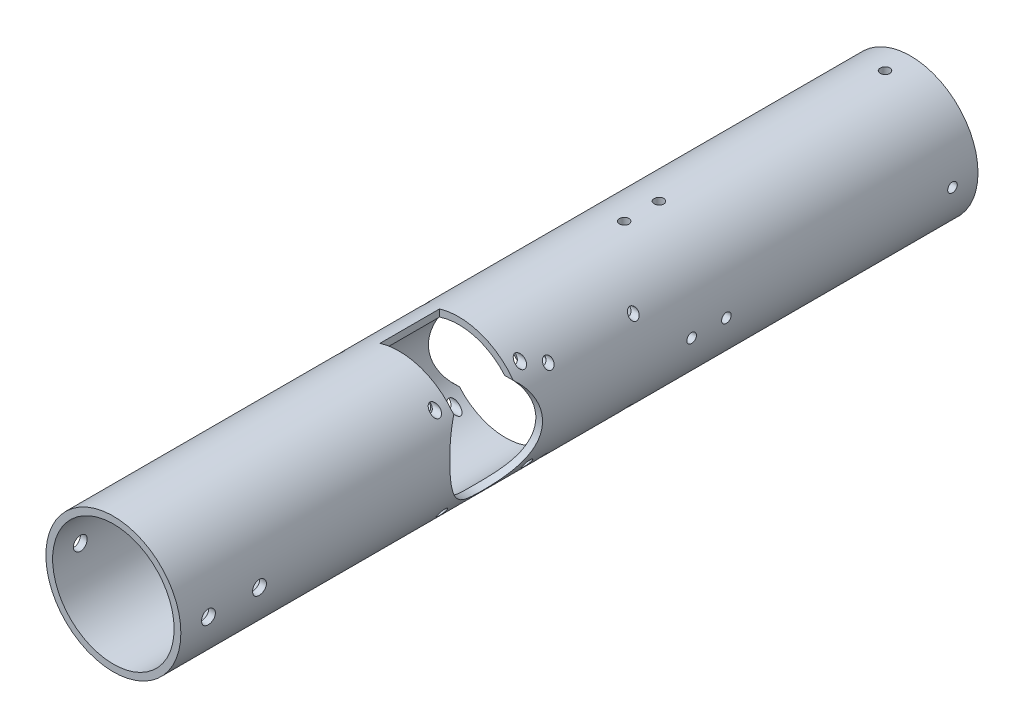
SolidWorks part; units mm, degrees
material "6061 Alloy"
ref_plane "Front Plane" through (0, 0, 0) normal (0, 0, 1) x (1, 0, 0)
ref_plane "Top Plane" through (0, 0, 0) normal (0, 1, 0) x (1, 0, 0)
ref_plane "Right Plane" through (0, 0, 0) normal (1, 0, 0) x (0, 0, -1)
sketch "Sketch1" plane through (0, 0, 0) normal (0, 0, 1) x (1, 0, 0)
  circle A0 centre (0, 0) radius 31.75
  circle A1 centre (0, 0) radius 28.575
  dimension "D1" = 63.5
  dimension "D2" = 57.15
extrude "Boss-Extrude1" add sketch "Sketch1" along normal blind 125 and the other way blind 250 contours A1 | A0 region at (0, 0, 0)
sketch "Sketch2" plane through (0, 0, 0) normal (1, 0, 0) x (0, 0, -1)
  circle A2 centre (73.488, -2) radius 21.75
  dimension "D1" = 43.5
  dimension "D2" = 73.488
  dimension "D3" = 2
extrude "Cut-Extrude1" cut sketch "Sketch2" against normal through all
sketch "Sketch3" plane through (0, 0, 0) normal (1, 0, 0) x (0, 0, -1)
  circle A1 centre (23.45, 2) radius 21.75
  dimension "D1" = 23.45
  dimension "D2" = 43.5
  dimension "D3" = 2
extrude "Cut-Extrude2" cut sketch "Sketch3" along normal through all
sketch "Sketch5" plane through (0, 0, 0) normal (1, 0, 0) x (0, 0, -1)
  line L1 (87.488, -12.75) -> (59.488, -12.75)
  line L2 (87.488, -12.75) -> (87.488, -34.75)
  line L3 (87.488, -34.75) -> (59.488, -34.75)
  line L4 (59.488, -12.75) -> (59.488, -34.75)
  line L5 (87.488, -12.75) -> (59.488, -34.75) construction
  line L6 (87.488, -34.75) -> (59.488, -12.75) construction
  circle A0 centre (73.488, -2) radius 21.75 construction
  circle A1 centre (73.488, -2) radius 21.75 construction
  circle A2 centre (73.488, -2) radius 21.75 construction
  point P0 (73.488, -23.75)
  dimension "D1" = 28
  dimension "D2" = 22
extrude "Cut-Extrude4" cut sketch "Sketch5" against normal through all from offset 9
sketch "Sketch6" plane through (0, 0, 0) normal (1, 0, 0) x (0, 0, -1)
  line L1 (9.45, 34.75) -> (37.45, 34.75)
  line L2 (9.45, 34.75) -> (9.45, 12.75)
  line L3 (9.45, 12.75) -> (37.45, 12.75)
  line L4 (37.45, 34.75) -> (37.45, 12.75)
  line L5 (9.45, 34.75) -> (37.45, 12.75) construction
  line L6 (9.45, 12.75) -> (37.45, 34.75) construction
  circle A0 centre (23.45, 2) radius 21.75 construction
  circle A1 centre (23.45, 2) radius 21.75 construction
  circle A2 centre (23.45, 2) radius 21.75 construction
  point P0 (23.45, 23.75)
  dimension "D1" = 28
  dimension "D2" = 22
extrude "Cut-Extrude5" cut sketch "Sketch6" along normal through all from offset 9 offset against normal yes
sketch "Sketch10" plane through (0, 0, 0) normal (1, 0, 0) x (0, 0, -1)
  line L1 (113.488, 38) -> (33.488, 38)
  line L2 (113.488, 38) -> (113.488, -42)
  line L3 (113.488, -42) -> (33.488, -42)
  line L4 (33.488, 38) -> (33.488, -42)
  line L5 (113.488, 38) -> (33.488, -42) construction
  line L6 (113.488, -42) -> (33.488, 38) construction
  point P0 (73.488, -2)
  dimension "D1" = 80
  dimension "D2" = 80
sketch "Sketch11" plane through (0, 0, 0) normal (1, 0, 0) x (0, 0, -1)
  line L0 (113.488, 38) -> (33.488, -42) construction
  line L1 (113.488, -42) -> (33.488, 38) construction
  line L2 (51.738, -2) -> (95.238, -2) construction
  line L3 (53.488, 18) -> (53.488, -22) construction
  circle A0 centre (93.488, 18) radius 2
  circle A1 centre (53.488, 18) radius 2
  circle A2 centre (53.488, -22) radius 2
  circle A3 centre (93.488, -22) radius 2
  arc A4 (87.488, -18.6452) -> (59.488, -18.6452) centre (73.488, -2) ccw construction
  arc A5 (87.488, -18.6452) -> (59.488, -18.6452) centre (73.488, -2) ccw construction
  point P18 (53.488, -2)
  dimension "D5" = 4
  dimension "D1" = 40
extrude "Cut-Extrude8" cut sketch "Sketch11" against normal through all both and the other way through all
sketch "Sketch12" plane through (0, 0, 0) normal (1, 0, 0) x (0, 0, -1)
  line L0 (-125, 31.75) -> (-125, -31.75) construction
  circle A0 centre (-112, 0) radius 3.25
  circle A1 centre (-88, 0) radius 3.25
  dimension "D2" = 6.5
  dimension "D3" = 24
  dimension "D4" = 13
extrude "Cut-Extrude10" cut sketch "Sketch12" against normal through all both and the other way through all
sketch "Sketch13" plane through (0, 0, 0) normal (0, 1, 0) x (1, 0, 0)
  line L0 (0, -34.925) -> (0, 34.925) construction
  line L1 (28.575, 250) -> (-28.575, 250) construction
  line L2 (0, 250) -> (0, -125) construction
  circle A0 centre (0, 238) radius 2.25
  circle A1 centre (0, 205.9) radius 2.25 construction
  dimension "D2" = 4.5
  dimension "D3" = 32.1
  dimension "D1" = 12
extrude "Cut-Extrude11" cut sketch "Sketch13" against normal through all both and the other way through all
sketch "Sketch14" plane through (0, 0, 0) normal (1, 0, 0) x (0, 0, -1)
  line L0 (3.45, -18) -> (3.45, 22) construction
  line L1 (-1.55, 27) -> (48.45, 27) construction
  line L2 (-1.55, 27) -> (-1.55, -23) construction
  line L3 (-1.55, -23) -> (48.45, -23) construction
  line L4 (48.45, 27) -> (48.45, -23) construction
  line L5 (-1.55, 27) -> (48.45, -23) construction
  line L6 (-1.55, -23) -> (48.45, 27) construction
  circle A0 centre (3.45, 22) radius 2
  circle A1 centre (43.45, 22) radius 2
  circle A2 centre (43.45, -18) radius 2
  circle A3 centre (3.45, -18) radius 2
  point P0 (23.45, 2)
  point P14 (3.45, 2)
  dimension "D5" = 4
  dimension "D1" = 40
  dimension "D2" = 50
sketch "Sketch15" plane through (0, 0, 0) normal (1, 0, 0) x (0, 0, -1)
  circle A0 centre (3.45, 22) radius 2
  circle A1 centre (43.45, 22) radius 2
  circle A2 centre (43.45, -18) radius 2
  circle A3 centre (3.45, -18) radius 2
  dimension "D1" = 4
extrude "Cut-Extrude12" cut sketch "Sketch15" against normal through all and the other way through all
hole_wizard "M4 Clearance Hole1" positions "Sketch18" profile "Sketch19" hole size "M4" standard "ANSI Metric" end condition through all
sketch "Sketch18" plane through (0, 0, 0) normal (1, 0, 0) x (0, 0, -1)
  circle A0 centre (3.45, 22) radius 2 construction
  circle A1 centre (43.45, 22) radius 2 construction
  circle A2 centre (3.45, -18) radius 2 construction
  circle A3 centre (43.45, -18) radius 2 construction
  point P0 (3.45, 22)
  point P2 (43.45, 22)
  point P4 (3.45, -18)
  point P6 (43.45, -18)
  point P20 (93.488, 18)
  point P23 (53.488, 18)
  point P26 (93.488, -22)
  point P29 (53.488, -22)
sketch "Sketch19" plane through (0, 22, -3.45) normal (0, 1, 0) x (0, 0, 1)
  line L0 (0, 0) -> (0, 31.75)
  line L1 (0, 31.75) -> (2.25, 31.75)
  line L2 (2.25, 31.75) -> (2.25, 0)
  line L5 (2.25, 0) -> (0, 0)
  line L11 (0, -6.35) -> (0, 107.95) construction
  dimension "Thru Hole Dia." = 4.5
  dimension "Thru Hole Depth" = 31.75
mirror "Mirror1" about plane through (0, 0, 0) normal (1, 0, 0) of "M4 Clearance Hole1"
sketch "Sketch21" plane through (0, 0, -250) normal (0, 0, -1) x (-1, 0, 0)
  circle A0 centre (0, 0) radius 30
  dimension "D1" = 60
extrude "Cut-Extrude14" cut sketch "Sketch21" against normal blind 7
pattern_circular "CirPattern1" count 2 every 90 about axis through (0, 0, -250) along (0, 0, 1) of "Cut-Extrude11"
sketch "Sketch22" plane through (0, 0, 0) normal (1, 0, 0) x (0, 0, -1)
  circle A0 centre (221.65, 0) radius 2.25 construction
  circle A1 centre (131.65, 0) radius 2.25
  circle A2 centre (115.3, 0) radius 2.25
  circle A3 centre (238, 0) radius 2.25 construction
  circle A4 centre (238, 0) radius 2.25 construction
  dimension "D1" = 16.35
  dimension "D2" = 106.35
  dimension "D3" = 122.7
extrude "Cut-Extrude15" cut sketch "Sketch22" along normal through all
pattern_circular "CirPattern2" count 4 over 360 about axis through (0, 0, -250) along (0, 0, 1) of "Cut-Extrude15"
